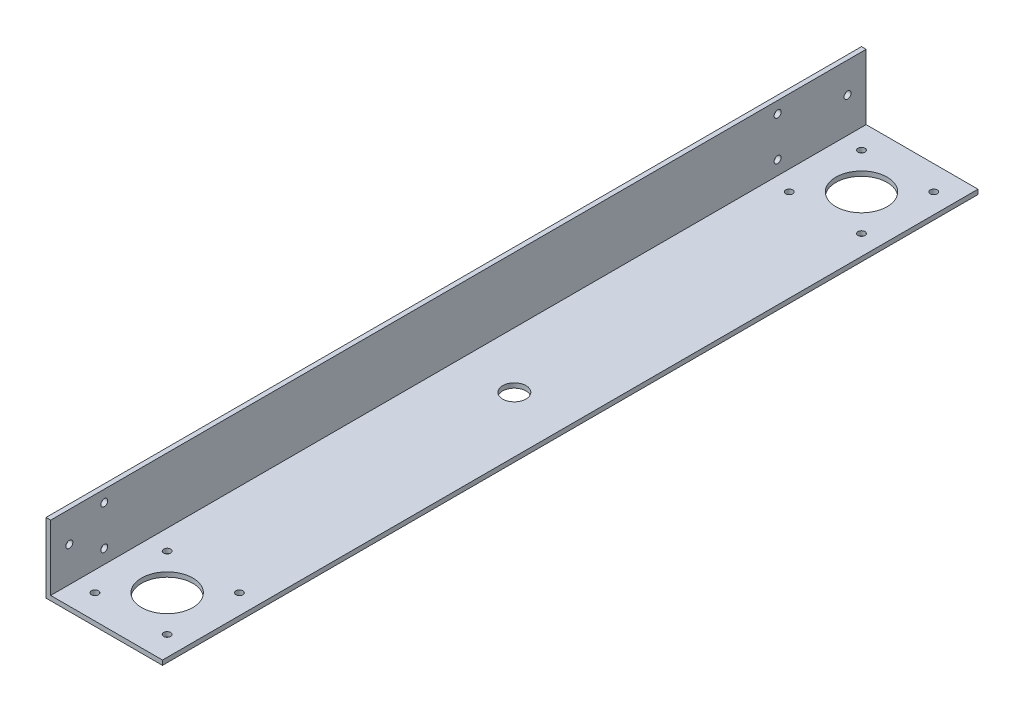
SolidWorks part; units mm, degrees
ref_plane "Front Plane" through (0, 0, 0) normal (0, 0, 1) x (1, 0, 0)
ref_plane "Top Plane" through (0, 0, 0) normal (0, 1, 0) x (1, 0, 0)
ref_plane "Right Plane" through (0, 0, 0) normal (1, 0, 0) x (0, 0, -1)
sketch "Sketch1" plane through (0, 0, 0) normal (0, 0, 1) x (1, 0, 0)
  line L0 (0, 0) -> (0, 30)
  line L1 (0, 30) -> (2, 30)
  line L2 (2, 30) -> (2, 2)
  line L3 (2, 2) -> (50, 2)
  line L4 (50, 2) -> (50, 0)
  line L5 (50, 0) -> (0, 0)
extrude "Boss-Extrude1" add sketch "Sketch1" along normal blind 350
sketch "Sketch6" plane through (0, 2, 0) normal (0, 1, 0) x (1, 0, 0)
  circle A0 centre (41.5, -339.5) radius 1.5
  circle A1 centre (10.5, -308.5) radius 1.5
  circle A2 centre (10.5, -339.5) radius 1.5
  circle A3 centre (41.5, -308.5) radius 1.5
extrude "Cut-Extrude3" cut sketch "Sketch6" against normal through all
sketch "Sketch7" plane through (0, 2, 0) normal (0, 1, 0) x (1, 0, 0)
  circle A0 centre (26, -324) radius 11
extrude "Cut-Extrude4" cut sketch "Sketch7" against normal through all
sketch "Sketch8" plane through (0, 0, 0) normal (0, -1, 0) x (-1, 0, 0)
  circle A0 centre (-26, -26) radius 11
extrude "Cut-Extrude5" cut sketch "Sketch8" against normal through all
sketch "Sketch9" plane through (0, 0, 0) normal (0, -1, 0) x (1, 0, 0)
  circle A0 centre (41.5, 41.5) radius 1.5
  circle A1 centre (10.5, 41.5) radius 1.5
  circle A2 centre (10.5, 10.5) radius 1.5
  circle A3 centre (41.5, 10.5) radius 1.5
extrude "Cut-Extrude6" cut sketch "Sketch9" against normal through all
sketch "Sketch10" plane through (0, 0, 0) normal (0, -1, 0) x (1, 0, 0)
  circle A0 centre (26, 175) radius 5
extrude "Cut-Extrude7" cut sketch "Sketch10" against normal through all
hole_wizard "Ø3.0 (3) Diameter Hole1" positions "Sketch11" profile "Sketch12" hole size "Ø3.0" standard "ISO"
sketch "Sketch11" plane through (0, 141.68, 221.138) normal (-1, 0, 0) x (0, 0, 1)
  point P0 (105.862, -133.68)
  point P1 (120.862, -124.68)
  point P2 (105.862, -116.68)
sketch "Sketch12" plane through (0, 8, 327) normal (0, 1, 0) x (0, 0, 1)
  line L0 (0, 0) -> (0, 1.999)
  line L1 (0, 1.999) -> (1.5, 1.999)
  line L2 (1.5, 1.999) -> (1.5, 0)
  line L3 (1.5, 0) -> (0, 0)
  line L4 (0, -6.35) -> (0, 107.95) construction
  dimension "Thru Hole Dia." = 3
  dimension "Thru Hole Depth" = 1.999
hole_wizard "Ø3.0 (3) Diameter Hole2" positions "Sketch13" profile "Sketch14" hole size "Ø3.0" standard "ISO"
sketch "Sketch13" plane through (0, 141.68, 221.138) normal (-1, 0, 0) x (0, 0, 1)
  point P0 (-183.138, -133.68)
  point P1 (-213.138, -124.7112)
  point P2 (-183.138, -116.68)
sketch "Sketch14" plane through (0, 8, 38) normal (0, 1, 0) x (0, 0, 1)
  line L0 (0, 0) -> (0, 1.999)
  line L1 (0, 1.999) -> (1.5, 1.999)
  line L2 (1.5, 1.999) -> (1.5, 0)
  line L3 (1.5, 0) -> (0, 0)
  line L4 (0, -6.35) -> (0, 107.95) construction
  dimension "Thru Hole Dia." = 3
  dimension "Thru Hole Depth" = 1.999
